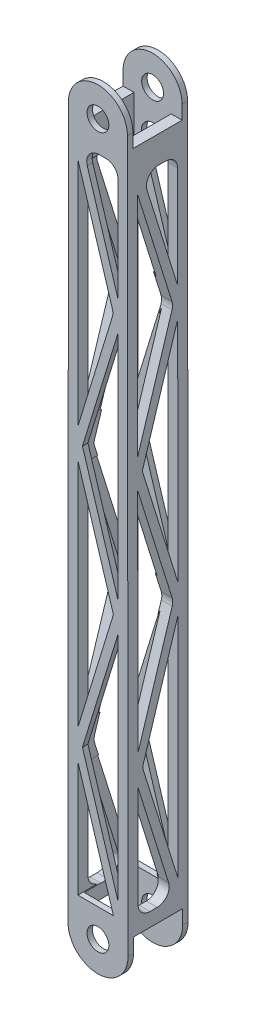
SolidWorks part; units mm, degrees
ref_plane "Front Plane" through (0, 0, 0) normal (0, 0, 1) x (1, 0, 0)
ref_plane "Top Plane" through (0, 0, 0) normal (0, 1, 0) x (1, 0, 0)
ref_plane "Right Plane" through (0, 0, 0) normal (1, 0, 0) x (0, 0, -1)
sketch "Sketch1" plane through (0, 0, 0) normal (0, 0, 1) x (1, 0, 0)
  line L0 (0, 0) -> (0, 650) construction
  line L1 (27, 650) -> (27.5, 0)
  line L2 (-27, 650) -> (-27.5, 0)
  line L3 (-27.49, 12.9767) -> (-17.49, 12.9767)
  line L4 (-17.49, 12.9767) -> (-17.0097, 637.4191)
  line L5 (-27.0097, 637.4191) -> (-17.0097, 637.4191)
  line L6 (-16.9839, 670.9893) -> (-16.6055, 1162.8403)
  line L7 (27.0097, 637.4191) -> (17.0097, 637.4191)
  line L8 (27.49, 12.9767) -> (17.49, 12.9767)
  line L9 (17.49, 12.9767) -> (17.0097, 637.4191)
  circle A0 centre (0, 0) radius 10
  arc A1 (-27.5, 0) -> (27.5, 0) centre (0, 0) ccw
  arc A2 (27, 650) -> (-27, 650) centre (0, 650) ccw
  circle A3 centre (0, 650) radius 10
  dimension "D1" = 20
  dimension "D2" = 55
  dimension "D4" = 20
  dimension "D5" = 54
  dimension "D3" = 650
  dimension "D6" = 10
extrude "Boss-Extrude2" add sketch "Sketch1" along normal blind 5 contours L1 A2 L2 L5 L4 L3 A1 L8 L9 L7 A0 A3 region at (0, 322.8762, 0)
extrude "Boss-Extrude3" add sketch "Sketch1<3>" along normal blind 55 contours L9 L8 L1 L7 | L5 L2 L3 L4 region at (22.2498, 325.1979, 0) region at (-22.2498, 325.1979, 0)
sketch "Sketch1<3>" plane through (0, 0, 0) normal (0, 0, 1) x (1, 0, 0) same geometry as "Sketch1"
extrude "Boss-Extrude4" add sketch "Sketch1<4>" along normal blind 5 from offset 50 contours L1 A2 L2 L5 L4 L3 A1 L8 L9 L7 A0 A3 region at (0, 322.8762, 0)
sketch "Sketch1<4>" plane through (0, 0, 0) normal (0, 0, 1) x (1, 0, 0) same geometry as "Sketch1"
sketch "Sketch3" plane through (27.5, 0.0212, 0) normal (1, 0.0008, 0) x (0, 0, -1)
  line L0 (-9.1513, 612.558) -> (-9.1513, 25.6)
  line L1 (-50, 637.3981) -> (-5, 637.3981) construction
  line L2 (-27.5, 637.3981) -> (-27.5, 612.558) construction
  line L3 (-9.1513, 612.558) -> (-45.8487, 612.558)
  line L4 (-45.8487, 612.558) -> (-9.1513, 495.166) construction
  line L5 (-9.1513, 25.6) -> (-45.8487, 25.6)
  line L6 (-45.8487, 612.558) -> (-45.8487, 25.6)
  line L7 (-27.5, 25.6) -> (-27.5, 0) construction
  line L8 (-9.1513, 495.166) -> (-45.8487, 495.166) construction
  line L9 (-45.8487, 377.774) -> (-9.1513, 495.166) construction
  line L10 (-45.8487, 377.774) -> (-9.1513, 377.774) construction
  line L11 (-45.8487, 377.774) -> (-9.1513, 260.382) construction
  line L12 (-9.1513, 260.382) -> (-45.8487, 260.382) construction
  line L13 (-45.8487, 142.99) -> (-9.1513, 260.382) construction
  line L14 (-45.8487, 142.99) -> (-9.1513, 142.99) construction
  line L15 (-45.8487, 142.99) -> (-9.1513, 25.598) construction
  line L16 (-41.6579, 612.558) -> (-9.1513, 508.5722)
  line L17 (-45.8487, 599.1517) -> (-13.3421, 495.166)
  line L18 (-41.6579, 377.774) -> (-9.1513, 481.7597)
  line L19 (-45.8487, 391.1802) -> (-13.3421, 495.166)
  line L20 (-41.6579, 377.774) -> (-9.1513, 273.7882)
  line L21 (-45.8487, 364.3677) -> (-13.3421, 260.382)
  line L22 (-45.8487, 156.3962) -> (-13.3421, 260.382)
  line L23 (-41.6579, 142.99) -> (-9.1513, 246.9757)
  line L24 (-41.6579, 142.99) -> (-9.1513, 39.0042)
  line L25 (-45.8487, 129.5837) -> (-13.3421, 25.598)
  dimension "D1" = 117.392
  dimension "D2" = 4
  dimension "D3" = 4
sketch "Sketch4" plane through (0, 0, 55) normal (0, 0, 1) x (1, 0, 0)
  line L0 (0, 677) -> (0, 622.1823) construction
  line L1 (0, 640) -> (0, 622.1823) construction
  line L2 (-18.35, 622.1823) -> (18.35, 502.8923) construction
  line L3 (18.35, 622.1823) -> (-18.35, 622.1823)
  line L4 (18.35, 502.8923) -> (-18.35, 502.8923) construction
  line L5 (18.35, 25.7331) -> (-18.35, 25.7331)
  line L6 (-18.35, 622.1823) -> (-18.35, 25.7331)
  line L7 (18.35, 622.1823) -> (18.35, 25.7331)
  line L8 (0, 25.7331) -> (0, -27.5) construction
  line L9 (0, 25.7331) -> (0, 10) construction
  line L10 (-18.35, 383.6023) -> (18.35, 502.8923) construction
  line L11 (-18.35, 383.6023) -> (18.35, 383.6023)
  line L12 (-18.35, 383.6023) -> (18.35, 264.3123) construction
  line L13 (18.35, 264.3123) -> (-18.35, 264.3123) construction
  line L14 (-18.35, 145.0223) -> (18.35, 264.3123) construction
  line L15 (-18.35, 145.0223) -> (18.35, 145.0223) construction
  line L16 (-18.35, 145.0223) -> (18.35, 25.7323) construction
  line L17 (-14.165, 622.1823) -> (18.35, 516.4953)
  line L18 (-18.35, 608.5792) -> (14.165, 502.8923)
  line L19 (-18.35, 397.2053) -> (14.165, 502.8923)
  line L20 (-14.165, 383.6023) -> (18.35, 489.2892)
  line L21 (-14.165, 383.6023) -> (18.35, 277.9153)
  line L22 (-18.35, 369.9992) -> (14.165, 264.3123)
  line L23 (-18.35, 158.6253) -> (14.165, 264.3123)
  line L24 (-14.165, 145.0223) -> (18.35, 250.7092)
  line L25 (-14.165, 145.0223) -> (18.35, 39.3353)
  line L26 (-18.35, 131.4192) -> (14.165, 25.7323)
  arc A0 (27, 650) -> (-27, 650) centre (0, 650) ccw construction
  arc A1 (-27.5, 0) -> (27.5, 0) centre (0, 0) ccw construction
  circle A6 centre (0, 650) radius 10 construction
  circle A7 centre (0, 0) radius 10 construction
  point P45 (18.0295, 622.1823)
  dimension "D1" = 119.29
  dimension "D2" = 4
  dimension "D3" = 4
extrude "Cut-Extrude2" cut sketch "Sketch3" against normal through all both and the other way through all contours L23 L24 L0 | L25 L6 L5 | L6 L22 L21 | L18 L20 L0 | L3 L16 L0 | L6 L19 L17 region at (27.0554, 577.917, 19.9868) region at (27.2094, 377.795, 19.9868) region at (27.1191, 495.187, 35.0132) region at (27.39, 143.0111, 19.9868) region at (27.2997, 260.403, 35.0132) region at (27.4536, 60.2824, 35.0134)
extrude "Cut-Extrude4" cut sketch "Sketch4" against normal through all both and the other way through all contours L6 L23 L22 | L11 L21 L7 | L24 L25 L7 | L6 L19 L18 | L20 L11 L7 | L3 L17 L7 | L26 L6 L5 region at (7.5117, 586.9533, 55) region at (7.5117, 418.8313, 55) region at (-7.5117, 502.8923, 55) region at (7.5117, 348.3733, 55) region at (7.5117, 145.0223, 55) region at (-7.5117, 264.3123, 55) region at (-7.5118, 60.9618, 55)
fillet "Fillet1" radius 11 17 edges at (-22.0288, 612.5412, 41.6579) (-22.0288, 612.5412, 9.1513) (22.4803, 25.6173, 13.3428) (22.4803, 25.6173, 45.8487) (-22.4803, 25.5827, 13.3428) (-22.4803, 25.5827, 45.8487) (22.87, 143.0076, 41.6579) (-22.39, 142.9728, 41.6579) (22.2997, 260.3992, 13.3421) (-22.8249, 260.3645, 13.3421) (22.1191, 495.1831, 13.3421) (-22.7346, 495.1486, 13.3421) (14.165, 502.8923, 2.5) (14.165, 502.8923, 52.5) (18.35, 622.1823, 27.5) (-14.165, 622.1823, 52.5) (-14.165, 622.1823, 2.5)
fillet "Fillet2" radius 11 2 edges at (22.6453, 612.5756, 9.1513) (22.6453, 612.5756, 41.6579)
